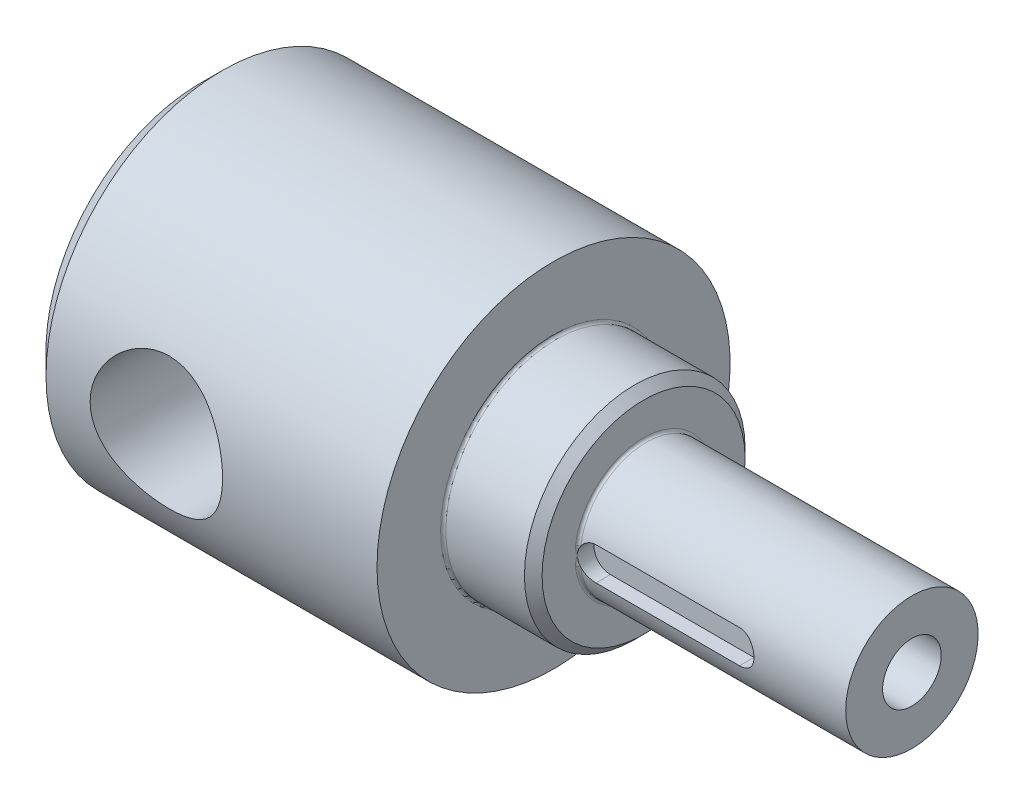
SolidWorks part; units mm, degrees
ref_plane "Front Plane" through (0, 0, 0) normal (0, 0, 1) x (1, 0, 0)
ref_plane "Top Plane" through (0, 0, 0) normal (0, 1, 0) x (1, 0, 0)
ref_plane "Right Plane" through (0, 0, 0) normal (1, 0, 0) x (0, 0, -1)
sketch "Sketch1" plane through (0, 0, 0) normal (0, 0, 1) x (1, 0, 0)
  line L0 (0, 0) -> (0, 9.525)
  line L1 (0, 9.525) -> (-38.608, 9.525)
  line L2 (-38.608, 9.525) -> (-38.608, 15.875)
  line L3 (-38.608, 15.875) -> (-51.562, 15.875)
  line L4 (-51.562, 15.875) -> (-51.562, 25.4)
  line L5 (-51.562, 25.4) -> (-102.362, 25.4)
  line L6 (-102.362, 25.4) -> (-102.362, 0)
  line L7 (-102.362, 0) -> (0, 0)
  dimension "D1" = 25.4
  dimension "D2" = 50.8
  dimension "D3" = 12.954
  dimension "D4" = 38.608
  dimension "D5" = 9.525
  dimension "D6" = 15.875
revolve "Revolve1" add sketch "Sketch1" angle 360 about L7
chamfer "Chamfer1" distance 3.175 angle 45 1 edges at (-102.362, 0, 25.4)
chamfer "Chamfer2" distance 1.27 angle 45 1 edges at (-38.608, 0, 15.875)
fillet "Fillet1" radius 0.381 1 edges at (-51.562, 0, 15.875)
sketch "Sketch2" plane through (0, 0, 0) normal (0, 0, 1) x (1, 0, 0)
  line L0 (-102.362, 22.225) -> (-102.362, -22.225) construction
  circle A0 centre (-83.312, 0) radius 9.525
  point P4 (0, 0)
  dimension "D1" = 19.05
  dimension "D2" = 19.05
extrude "Cut-Extrude1" cut sketch "Sketch2" against normal through all both and the other way through all
ref_plane "Plane1" through (0, 0, 9.525) normal (0, 0, 1) x (1, 0, 0)
sketch "Sketch3" plane through (0, 0, 9.525) normal (0, 0, 1) x (1, 0, 0)
  line L0 (0, 0) -> (-38.608, 0) construction
  line L1 (-38.608, -9.525) -> (-38.608, 9.525) construction
  line L2 (-36.2267, 0) -> (-15.5892, 0) construction
  line L3 (-36.2267, 2.3812) -> (-15.5892, 2.3813)
  line L4 (-36.2267, -2.3813) -> (-15.5892, -2.3813)
  arc A0 (-36.2267, 2.3812) -> (-36.2267, -2.3813) centre (-36.2267, 0) ccw
  arc A1 (-15.5892, -2.3813) -> (-15.5892, 2.3813) centre (-15.5892, 0) ccw
  point P7 (-25.908, 0)
  dimension "D2" = 2.3812
  dimension "D1" = 20.6375
extrude "Cut-Extrude2" cut sketch "Sketch3" against normal blind 2.3813 and the other way blind 2.3813
fillet "Fillet2" radius 0.381 1 edges at (-38.608, 0, 9.525)
hole_wizard "3/8-24 Tapped Hole1" positions "Sketch4" profile "Sketch5" tap size "3/8-24" standard "ANSI Inch"
sketch "Sketch4" plane through (0, 0, 0) normal (1, 0, 0) x (0, 0, -1)
  point P0 (0, 0)
sketch "Sketch5" plane through (0, 0, 0) normal (0, 1, 0) x (0, 0, -1)
  line L0 (0, 0) -> (0, 27.9335)
  line L1 (0, 27.9335) -> (4.2164, 25.4)
  line L2 (4.2164, 25.4) -> (4.2164, 0)
  line L5 (4.2164, 0) -> (0, 0)
  line L10 (0, 27.9335) -> (-4.2164, 25.4) construction
  line L11 (0, -6.35) -> (0, 107.95) construction
  dimension "Tap Drill Dia." = 8.4328
  dimension "Tap Drill Depth" = 25.4
  dimension "Drill Angle" = 118
cosmetic thread "Hole Thread1" parameters "D1"=19.05, "D2"=9.525
